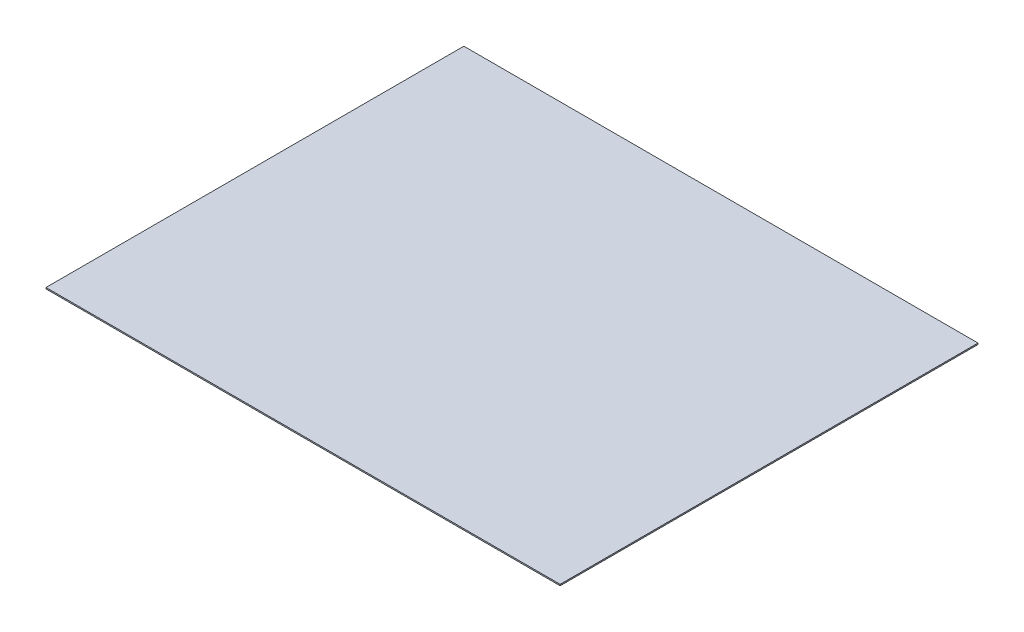
SolidWorks part; units mm, degrees
ref_plane "Front Plane" through (0, 0, 0) normal (0, 0, 1) x (1, 0, 0)
ref_plane "Top Plane" through (0, 0, 0) normal (0, 1, 0) x (1, 0, 0)
ref_plane "Right Plane" through (0, 0, 0) normal (1, 0, 0) x (0, 0, -1)
sketch "Sketch1" plane through (0, 0, 0) normal (0, 1, 0) x (1, 0, 0)
  line L1 (0, 0) -> (625.602, 0)
  line L2 (0, 0) -> (0, 508.4572)
  line L3 (0, 508.4572) -> (625.602, 508.4572)
  line L4 (625.602, 0) -> (625.602, 508.4572)
  dimension "D1" = 508.4572
  dimension "D2" = 625.602
extrude "Boss-Extrude1" add sketch "Sketch1" along normal blind 1.5875
